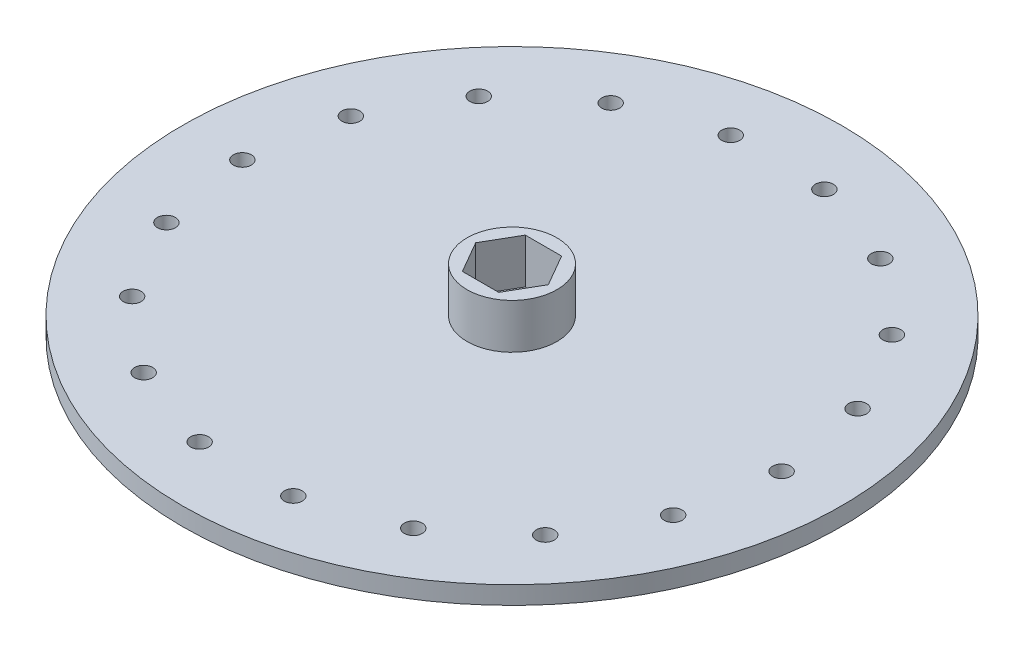
SolidWorks part; units mm, degrees
material "ABS"
ref_plane "Front Plane" through (0, 0, 0) normal (0, 0, 1) x (1, 0, 0)
ref_plane "Top Plane" through (0, 0, 0) normal (0, 1, 0) x (1, 0, 0)
ref_plane "Right Plane" through (0, 0, 0) normal (1, 0, 0) x (0, 0, -1)
sketch "Sketch1" plane through (0, 0, 0) normal (0, 1, 0) x (1, 0, 0)
  line L0 (0, 0) -> (-110, 0) construction
  line L1 (-108.3289, 19.1013) -> (-63.9629, 11.2784) construction
  circle A0 centre (0, 0) radius 110
  circle A1 centre (-90, 0) radius 3
  circle A2 centre (-84.5723, 30.7818) radius 3
  circle A3 centre (-68.944, 57.8509) radius 3
  circle A4 centre (-45, 77.9423) radius 3
  circle A5 centre (-15.6283, 88.6327) radius 3
  circle A6 centre (15.6283, 88.6327) radius 3
  circle A7 centre (45, 77.9423) radius 3
  circle A8 centre (68.944, 57.8509) radius 3
  circle A9 centre (84.5723, 30.7818) radius 3
  circle A10 centre (90, 0) radius 3
  circle A11 centre (84.5723, -30.7818) radius 3
  circle A12 centre (68.944, -57.8509) radius 3
  circle A13 centre (45, -77.9423) radius 3
  circle A14 centre (15.6283, -88.6327) radius 3
  circle A15 centre (-15.6283, -88.6327) radius 3
  circle A16 centre (-45, -77.9423) radius 3
  circle A17 centre (-68.944, -57.8509) radius 3
  circle A18 centre (-84.5723, -30.7818) radius 3
  circle A19 centre (0, 0) radius 7.25
  point P43 (0, 0)
  dimension "D1" = 220
  dimension "D2" = 6
  dimension "D5" = 14.5
  dimension "D3" = 90
  dimension "D6" = 10
  dimension "D4" = 18
extrude "Boss-Extrude1" add sketch "Sketch1" along normal blind 6
sketch "Sketch2" plane through (0, 6, 0) normal (0, 1, 0) x (1, 0, 0)
  line L1 (-87.0349, 24.016) -> (-79.9443, 25.2663)
  line L2 (-90, -7.2) -> (-83.7646, -3.6)
  line L3 (-83.7646, -3.6) -> (-83.7646, 3.6)
  line L4 (-83.7646, 3.6) -> (-90, 7.2)
  line L5 (-90, 7.2) -> (-96.2354, 3.6)
  line L6 (-96.2354, 3.6) -> (-96.2354, -3.6)
  line L7 (-96.2354, -3.6) -> (-90, -7.2)
  line L8 (-79.9443, 25.2663) -> (-77.4817, 32.0321)
  line L9 (-77.4817, 32.0321) -> (-82.1098, 37.5476)
  line L10 (-82.1098, 37.5476) -> (-89.2004, 36.2973)
  line L11 (-89.2004, 36.2973) -> (-91.663, 29.5315)
  line L12 (-91.663, 29.5315) -> (-87.0349, 24.016)
  line L13 (-73.5721, 52.3354) -> (-66.4815, 51.0851)
  line L14 (-66.4815, 51.0851) -> (-61.8534, 56.6006)
  line L15 (-61.8534, 56.6006) -> (-64.3159, 63.3664)
  line L16 (-64.3159, 63.3664) -> (-71.4065, 64.6167)
  line L17 (-71.4065, 64.6167) -> (-76.0346, 59.1012)
  line L18 (-76.0346, 59.1012) -> (-73.5721, 52.3354)
  line L19 (-51.2354, 74.3423) -> (-45, 70.7423)
  line L20 (-45, 70.7423) -> (-38.7646, 74.3423)
  line L21 (-38.7646, 74.3423) -> (-38.7646, 81.5423)
  line L22 (-38.7646, 81.5423) -> (-45, 85.1423)
  line L23 (-45, 85.1423) -> (-51.2354, 81.5423)
  line L24 (-51.2354, 81.5423) -> (-51.2354, 74.3423)
  line L25 (-22.719, 87.3824) -> (-18.0909, 81.8669)
  line L26 (-18.0909, 81.8669) -> (-11.0003, 83.1172)
  line L27 (-11.0003, 83.1172) -> (-8.5377, 89.883)
  line L28 (-8.5377, 89.883) -> (-13.1658, 95.3985)
  line L29 (-13.1658, 95.3985) -> (-20.2564, 94.1482)
  line L30 (-20.2564, 94.1482) -> (-22.719, 87.3824)
  line L31 (8.5377, 89.883) -> (11.0003, 83.1172)
  line L32 (11.0003, 83.1172) -> (18.0909, 81.8669)
  line L33 (18.0909, 81.8669) -> (22.719, 87.3824)
  line L34 (22.719, 87.3824) -> (20.2564, 94.1482)
  line L35 (20.2564, 94.1482) -> (13.1658, 95.3985)
  line L36 (13.1658, 95.3985) -> (8.5377, 89.883)
  line L37 (38.7646, 81.5423) -> (38.7646, 74.3423)
  line L38 (38.7646, 74.3423) -> (45, 70.7423)
  line L39 (45, 70.7423) -> (51.2354, 74.3423)
  line L40 (51.2354, 74.3423) -> (51.2354, 81.5423)
  line L41 (51.2354, 81.5423) -> (45, 85.1423)
  line L42 (45, 85.1423) -> (38.7646, 81.5423)
  line L43 (64.3159, 63.3664) -> (61.8534, 56.6006)
  line L44 (61.8534, 56.6006) -> (66.4815, 51.0851)
  line L45 (66.4815, 51.0851) -> (73.5721, 52.3354)
  line L46 (73.5721, 52.3354) -> (76.0346, 59.1012)
  line L47 (76.0346, 59.1012) -> (71.4065, 64.6167)
  line L48 (71.4065, 64.6167) -> (64.3159, 63.3664)
  line L49 (82.1098, 37.5476) -> (77.4817, 32.0321)
  line L50 (77.4817, 32.0321) -> (79.9443, 25.2663)
  line L51 (79.9443, 25.2663) -> (87.0349, 24.016)
  line L52 (87.0349, 24.016) -> (91.663, 29.5315)
  line L53 (91.663, 29.5315) -> (89.2004, 36.2973)
  line L54 (89.2004, 36.2973) -> (82.1098, 37.5476)
  line L55 (90, 7.2) -> (83.7646, 3.6)
  line L56 (83.7646, 3.6) -> (83.7646, -3.6)
  line L57 (83.7646, -3.6) -> (90, -7.2)
  line L58 (90, -7.2) -> (96.2354, -3.6)
  line L59 (96.2354, -3.6) -> (96.2354, 3.6)
  line L60 (96.2354, 3.6) -> (90, 7.2)
  line L61 (87.0349, -24.016) -> (79.9443, -25.2663)
  line L62 (79.9443, -25.2663) -> (77.4817, -32.0321)
  line L63 (77.4817, -32.0321) -> (82.1098, -37.5476)
  line L64 (82.1098, -37.5476) -> (89.2004, -36.2973)
  line L65 (89.2004, -36.2973) -> (91.663, -29.5315)
  line L66 (91.663, -29.5315) -> (87.0349, -24.016)
  line L67 (73.5721, -52.3354) -> (66.4815, -51.0851)
  line L68 (66.4815, -51.0851) -> (61.8534, -56.6006)
  line L69 (61.8534, -56.6006) -> (64.3159, -63.3664)
  line L70 (64.3159, -63.3664) -> (71.4065, -64.6167)
  line L71 (71.4065, -64.6167) -> (76.0346, -59.1012)
  line L72 (76.0346, -59.1012) -> (73.5721, -52.3354)
  line L73 (51.2354, -74.3423) -> (45, -70.7423)
  line L74 (45, -70.7423) -> (38.7646, -74.3423)
  line L75 (38.7646, -74.3423) -> (38.7646, -81.5423)
  line L76 (38.7646, -81.5423) -> (45, -85.1423)
  line L77 (45, -85.1423) -> (51.2354, -81.5423)
  line L78 (51.2354, -81.5423) -> (51.2354, -74.3423)
  line L79 (22.719, -87.3824) -> (18.0909, -81.8669)
  line L80 (18.0909, -81.8669) -> (11.0003, -83.1172)
  line L81 (11.0003, -83.1172) -> (8.5377, -89.883)
  line L82 (8.5377, -89.883) -> (13.1658, -95.3985)
  line L83 (13.1658, -95.3985) -> (20.2564, -94.1482)
  line L84 (20.2564, -94.1482) -> (22.719, -87.3824)
  line L85 (-8.5377, -89.883) -> (-11.0003, -83.1172)
  line L86 (-11.0003, -83.1172) -> (-18.0909, -81.8669)
  line L87 (-18.0909, -81.8669) -> (-22.719, -87.3824)
  line L88 (-22.719, -87.3824) -> (-20.2564, -94.1482)
  line L89 (-20.2564, -94.1482) -> (-13.1658, -95.3985)
  line L90 (-13.1658, -95.3985) -> (-8.5377, -89.883)
  line L91 (-38.7646, -81.5423) -> (-38.7646, -74.3423)
  line L92 (-38.7646, -74.3423) -> (-45, -70.7423)
  line L93 (-45, -70.7423) -> (-51.2354, -74.3423)
  line L94 (-51.2354, -74.3423) -> (-51.2354, -81.5423)
  line L95 (-51.2354, -81.5423) -> (-45, -85.1423)
  line L96 (-45, -85.1423) -> (-38.7646, -81.5423)
  line L97 (-64.3159, -63.3664) -> (-61.8534, -56.6006)
  line L98 (-61.8534, -56.6006) -> (-66.4815, -51.0851)
  line L99 (-66.4815, -51.0851) -> (-73.5721, -52.3354)
  line L100 (-73.5721, -52.3354) -> (-76.0346, -59.1012)
  line L101 (-76.0346, -59.1012) -> (-71.4065, -64.6167)
  line L102 (-71.4065, -64.6167) -> (-64.3159, -63.3664)
  line L103 (-82.1098, -37.5476) -> (-77.4817, -32.0321)
  line L104 (-77.4817, -32.0321) -> (-79.9443, -25.2663)
  line L105 (-79.9443, -25.2663) -> (-87.0349, -24.016)
  line L106 (-87.0349, -24.016) -> (-91.663, -29.5315)
  line L107 (-91.663, -29.5315) -> (-89.2004, -36.2973)
  line L108 (-89.2004, -36.2973) -> (-82.1098, -37.5476)
  line L241 (-90, 7.2) -> (-90, -7.2) construction
  circle A0 centre (0, 0) radius 90 construction
  circle A1 centre (-90, 0) radius 6.2354 construction
  dimension "D1" = 180
  dimension "D2" = 14.4
  dimension "D3" = 18
extrude "Cut-Extrude1" [suppressed] cut sketch "Sketch2" against normal blind 6 from offset 2 offset against normal yes
sketch "Sketch3" plane through (0, 6, 0) normal (0, 1, 0) x (1, 0, 0)
  line L13 (-6.0622, 10.5) -> (-12.1244, 0)
  line L14 (-12.1244, 0) -> (-6.0622, -10.5)
  line L15 (-6.0622, -10.5) -> (6.0622, -10.5)
  line L16 (6.0622, -10.5) -> (12.1244, 0)
  line L17 (12.1244, 0) -> (6.0622, 10.5)
  line L18 (6.0622, 10.5) -> (-6.0622, 10.5)
  circle A0 centre (0, 0) radius 15
  circle A1 centre (0, 0) radius 10.5 construction
  circle A3 centre (0, 0) radius 110
  circle A4 centre (0, 0) radius 110
  dimension "D1" = 0
  dimension "D2" = 30
  dimension "D3" = 21
extrude "Boss-Extrude2" add sketch "Sketch3" along normal blind 15 contours A0 | L16 L17 L18 L13 L14 L15
sketch "Sketch4" [suppressed] plane through (0, 6, 0) normal (0, 1, 0) x (1, 0, 0)
  line L0 (0, 0) -> (-44.5723, -122.4613) construction
  line L1 (-45, -77.9423) -> (0, 0) construction
  arc A0 (-47.125, -81.6229) -> (-16.3663, -92.8181) centre (0, 0) ccw
  arc A1 (-42.875, -74.2617) -> (-14.8903, -84.4473) centre (0, 0) ccw
  arc A7 (-42.875, -74.2617) -> (-47.125, -81.6229) centre (-45, -77.9423) ccw
  circle A8 centre (-45, -77.9423) radius 4.25 construction
  arc A9 (-14.8903, -84.4473) -> (-16.3663, -92.8181) centre (-15.6283, -88.6327) cw
  dimension "D1" = 10
  dimension "D3" = 85.75
  dimension "D4" = 94.25
sketch "Sketch5" plane through (0, 6, 0) normal (0, 1, 0) x (1, 0, 0)
  line L0 (0, 123.2166) -> (0, -127.0451) construction
  line L1 (-138.1229, 0) -> (170.7938, 0) construction
  line L2 (0, 0) -> (-121.3085, -44.1527) construction
  line L3 (0, 0) -> (-142.855, -25.1892) construction
  line L4 (0, 0) -> (-112.1352, -64.7413) construction
  line L6 (-72.0068, -13.7122) -> (-102.5961, -19.1059)
  line L7 (-63.9744, -35.7809) -> (-90.8742, -51.3116)
  line L8 (0.1736, -0.9848) -> (-142.6813, -26.174) construction
  arc A0 (-97.1344, -49.4562) -> (-106.1991, -24.5511) centre (0, 0) cw
  arc A1 (-72.0068, -13.7122) -> (-66.8646, -17.033) centre (-71.2254, -18.1438) cw
  arc A2 (-66.8646, -17.033) -> (-62.1698, -29.9318) centre (0, 0) ccw
  arc A3 (-62.1698, -29.9318) -> (-63.9744, -35.7809) centre (-66.2244, -31.8838) cw
  arc A4 (-97.1344, -49.4562) -> (-90.8742, -51.3116) centre (-93.1242, -47.4144) ccw
  arc A5 (-106.1991, -24.5511) -> (-102.5961, -19.1059) centre (-101.8147, -23.5375) cw
  dimension "D6" = 109
  dimension "D7" = 69
  dimension "D8" = 4.5
  dimension "D1" = 20
  dimension "D2" = 10
  dimension "D3" = 10
  dimension "D5" = 1
sketch "Sketch6" plane through (0, 6, 0) normal (0, 1, 0) x (1, 0, 0)
  line L0 (-115.4017, 0) -> (0, 0) construction
  line L1 (-108.5173, 18) -> (-69.1218, 11.0535) construction
  line L2 (-108.5173, -18) -> (-69.1218, -11.0535) construction
  line L3 (-95.8165, 54.0296) -> (-61.1727, 34.0279) construction
  line L4 (-108.1292, 20.2006) -> (-68.7337, 13.2541) construction
  line L5 (-71.5589, 83.5424) -> (-45.8453, 52.8981) construction
  line L6 (-94.6992, 55.9648) -> (-60.0554, 35.9631) construction
  line L7 (-38.6702, 102.9787) -> (-24.9883, 65.388) construction
  line L8 (-69.8471, 84.9787) -> (-44.1335, 54.3345) construction
  line L9 (-1.1173, 109.9943) -> (-1.1173, 69.9911) construction
  line L10 (-36.5704, 103.743) -> (-22.8885, 66.1522) construction
  line L11 (36.5704, 103.743) -> (22.8885, 66.1522) construction
  line L12 (1.1173, 109.9943) -> (1.1173, 69.9911) construction
  line L13 (69.8471, 84.9787) -> (44.1335, 54.3345) construction
  line L14 (38.6702, 102.9787) -> (24.9883, 65.388) construction
  line L15 (94.6992, 55.9648) -> (60.0554, 35.9631) construction
  line L16 (71.5589, 83.5424) -> (45.8453, 52.8981) construction
  line L17 (108.1292, 20.2006) -> (68.7337, 13.2541) construction
  line L18 (95.8165, 54.0296) -> (61.1727, 34.0279) construction
  line L19 (108.5173, -18) -> (69.1218, -11.0535) construction
  line L20 (108.5173, 18) -> (69.1218, 11.0535) construction
  line L21 (95.8165, -54.0296) -> (61.1727, -34.0279) construction
  line L22 (108.1292, -20.2006) -> (68.7337, -13.2541) construction
  line L23 (71.5589, -83.5424) -> (45.8453, -52.8981) construction
  line L24 (94.6992, -55.9648) -> (60.0554, -35.9631) construction
  line L25 (38.6702, -102.9787) -> (24.9883, -65.388) construction
  line L26 (69.8471, -84.9787) -> (44.1335, -54.3345) construction
  line L27 (1.1173, -109.9943) -> (1.1173, -69.9911) construction
  line L28 (36.5704, -103.743) -> (22.8885, -66.1522) construction
  line L29 (-36.5704, -103.743) -> (-22.8885, -66.1522) construction
  line L30 (-1.1173, -109.9943) -> (-1.1173, -69.9911) construction
  line L31 (-69.8471, -84.9787) -> (-44.1335, -54.3345) construction
  line L32 (-38.6702, -102.9787) -> (-24.9883, -65.388) construction
  line L33 (-94.6992, -55.9648) -> (-60.0554, -35.9631) construction
  line L34 (-71.5589, -83.5424) -> (-45.8453, -52.8981) construction
  line L35 (-108.1292, -20.2006) -> (-68.7337, -13.2541) construction
  line L36 (-95.8165, -54.0296) -> (-61.1727, -34.0279) construction
  circle A0 centre (0, 0) radius 110 construction
  arc A1 (-69.1218, 11.0535) -> (-69.1218, -11.0535) centre (0, 0) ccw construction
  arc A2 (-88.8199, 14.5268) -> (-88.8199, -14.5268) centre (0, 0) ccw construction
  arc A4 (-108.5173, -18) -> (-108.5173, 18) centre (0, 0) cw construction
  arc A5 (-108.1292, 20.2006) -> (-95.8165, 54.0296) centre (0, 0) cw construction
  arc A6 (-61.1727, 34.0279) -> (-68.7337, 13.2541) centre (0, 0) ccw construction
  arc A7 (-94.6992, 55.9648) -> (-71.5589, 83.5424) centre (0, 0) cw construction
  arc A8 (-45.8453, 52.8981) -> (-60.0554, 35.9631) centre (0, 0) ccw construction
  arc A9 (-69.8471, 84.9787) -> (-38.6702, 102.9787) centre (0, 0) cw construction
  arc A10 (-24.9883, 65.388) -> (-44.1335, 54.3345) centre (0, 0) ccw construction
  arc A11 (-36.5704, 103.743) -> (-1.1173, 109.9943) centre (0, 0) cw construction
  arc A12 (-1.1173, 69.9911) -> (-22.8885, 66.1522) centre (0, 0) ccw construction
  arc A13 (1.1173, 109.9943) -> (36.5704, 103.743) centre (0, 0) cw construction
  arc A14 (22.8885, 66.1522) -> (1.1173, 69.9911) centre (0, 0) ccw construction
  arc A15 (38.6702, 102.9787) -> (69.8471, 84.9787) centre (0, 0) cw construction
  arc A16 (44.1335, 54.3345) -> (24.9883, 65.388) centre (0, 0) ccw construction
  arc A17 (71.5589, 83.5424) -> (94.6992, 55.9648) centre (0, 0) cw construction
  arc A18 (60.0554, 35.9631) -> (45.8453, 52.8981) centre (0, 0) ccw construction
  arc A19 (95.8165, 54.0296) -> (108.1292, 20.2006) centre (0, 0) cw construction
  arc A20 (68.7337, 13.2541) -> (61.1727, 34.0279) centre (0, 0) ccw construction
  arc A21 (108.5173, 18) -> (108.5173, -18) centre (0, 0) cw construction
  arc A22 (69.1218, -11.0535) -> (69.1218, 11.0535) centre (0, 0) ccw construction
  arc A23 (108.1292, -20.2006) -> (95.8165, -54.0296) centre (0, 0) cw construction
  arc A24 (61.1727, -34.0279) -> (68.7337, -13.2541) centre (0, 0) ccw construction
  arc A25 (94.6992, -55.9648) -> (71.5589, -83.5424) centre (0, 0) cw construction
  arc A26 (45.8453, -52.8981) -> (60.0554, -35.9631) centre (0, 0) ccw construction
  arc A27 (69.8471, -84.9787) -> (38.6702, -102.9787) centre (0, 0) cw construction
  arc A28 (24.9883, -65.388) -> (44.1335, -54.3345) centre (0, 0) ccw construction
  arc A29 (36.5704, -103.743) -> (1.1173, -109.9943) centre (0, 0) cw construction
  arc A30 (1.1173, -69.9911) -> (22.8885, -66.1522) centre (0, 0) ccw construction
  arc A31 (-1.1173, -109.9943) -> (-36.5704, -103.743) centre (0, 0) cw construction
  arc A32 (-22.8885, -66.1522) -> (-1.1173, -69.9911) centre (0, 0) ccw construction
  arc A33 (-38.6702, -102.9787) -> (-69.8471, -84.9787) centre (0, 0) cw construction
  arc A34 (-44.1335, -54.3345) -> (-24.9883, -65.388) centre (0, 0) ccw construction
  arc A35 (-71.5589, -83.5424) -> (-94.6992, -55.9648) centre (0, 0) cw construction
  arc A36 (-60.0554, -35.9631) -> (-45.8453, -52.8981) centre (0, 0) ccw construction
  arc A37 (-95.8165, -54.0296) -> (-108.1292, -20.2006) centre (0, 0) cw construction
  arc A38 (-68.7337, -13.2541) -> (-61.1727, -34.0279) centre (0, 0) ccw construction
  point P13 (-90, 0)
  point P83 (0, 0)
  dimension "D2" = 90
  dimension "D3" = 70
  dimension "D4" = 110
  dimension "D1" = 10
  dimension "D6" = 18
